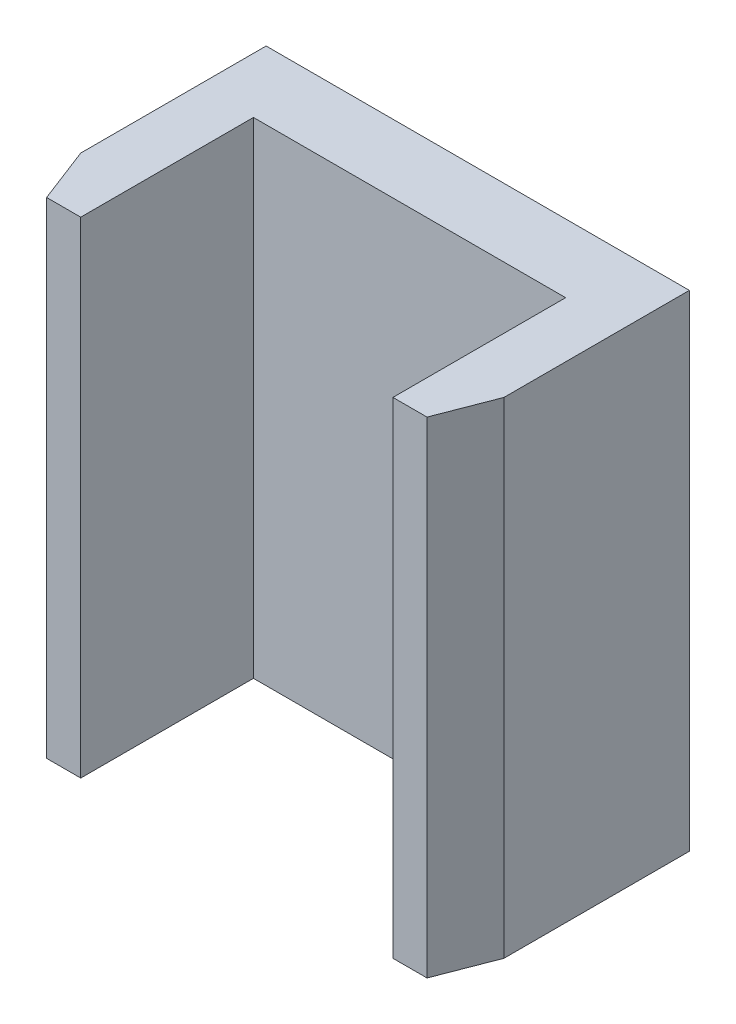
SolidWorks part; units mm, degrees
ref_plane "Front Plane" through (0, 0, 0) normal (0, 0, 1) x (1, 0, 0)
ref_plane "Top Plane" through (0, 0, 0) normal (0, 1, 0) x (1, 0, 0)
ref_plane "Right Plane" through (0, 0, 0) normal (1, 0, 0) x (0, 0, -1)
sketch "Sketch1" plane through (0, 0, 0) normal (1, 0, 0) x (0, 0, -1)
  line L1 (0, 0) -> (55.1, 0)
  line L2 (0, 0) -> (0, 111.1)
  line L3 (0, 111.1) -> (55.1, 111.1)
  line L4 (55.1, 0) -> (55.1, 111.1)
  dimension "D1" = 55.1
  dimension "D2" = 111.1
extrude "Boss-Extrude1" add sketch "Sketch1" along normal blind 12.7
sketch "Sketch2" plane through (0, 0, 0) normal (-1, 0, 0) x (0, 0, 1)
  line L0 (0, 111.1) -> (-39.5, 111.1) construction
  line L1 (-55.1, 111.1) -> (0, 111.1) construction
  line L3 (-39.5, 111.1) -> (-55.1, 111.1)
  line L4 (-39.5, 111.1) -> (-39.5, 0)
  line L5 (-39.5, 0) -> (-55.1, 0)
  line L6 (-55.1, 111.1) -> (-55.1, 0)
  dimension "D1" = 39.5
extrude "Boss-Extrude2" add sketch "Sketch2" along normal blind 71.4 contours L4 L3 L6 L5
sketch "Sketch4" plane through (-71.4, 0, 0) normal (-1, 0, 0) x (0, 0, 1)
  line L1 (-55.1, 111.1) -> (0, 111.1)
  line L2 (-55.1, 111.1) -> (-55.1, 0)
  line L3 (-55.1, 0) -> (0, 0)
  line L4 (0, 111.1) -> (0, 0)
extrude "Boss-Extrude3" add sketch "Sketch4" along normal blind 12.7 contours L2 L1 L4 L3
sketch "Sketch5" plane through (0, 111.1, 0) normal (0, 1, 0) x (1, 0, 0)
  line L0 (0, 0) -> (7.8, 0) construction
  line L1 (12.7, 0) -> (0, 0) construction
  line L2 (12.7, 0) -> (12.7, 12.7)
  line L3 (12.7, 55.1) -> (12.7, 0) construction
  line L4 (7.8, 0) -> (12.7, 12.7)
  line L5 (7.8, 0) -> (12.7, 0)
  line L6 (-71.4, 0) -> (-79.2, 0) construction
  line L7 (-84.1, 0) -> (-71.4, 0) construction
  line L8 (-84.1, 0) -> (-84.1, 12.7)
  line L9 (-84.1, 55.1) -> (-84.1, 0) construction
  line L10 (-84.1, 12.7) -> (-79.2, 0)
  line L11 (-79.2, 0) -> (-84.1, 0)
  dimension "D1" = 7.8
  dimension "D2" = 12.7
  dimension "D3" = 7.8
  dimension "D4" = 12.7
extrude "Cut-Extrude2" cut sketch "Sketch5" against normal through all
